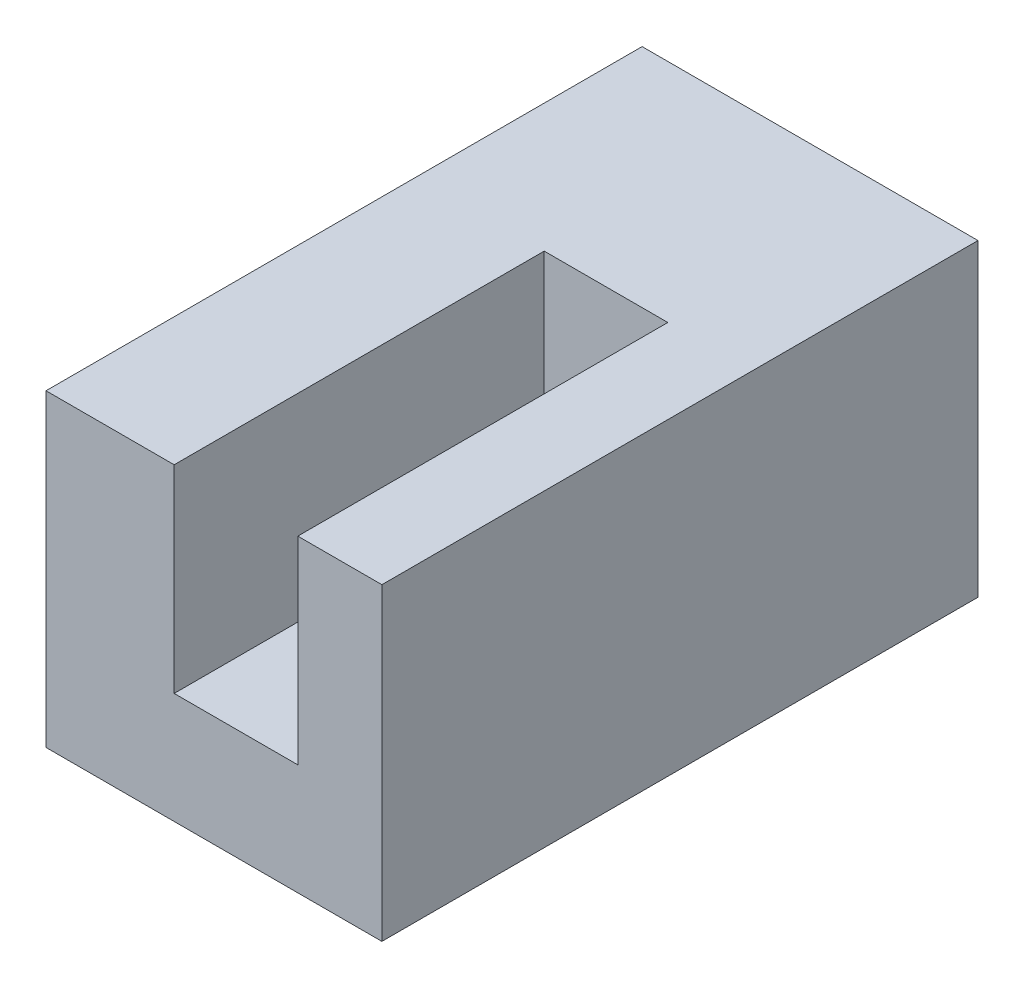
SolidWorks part; units mm, degrees
ref_plane "Piano frontale" through (0, 0, 0) normal (0, 0, 1) x (1, 0, 0)
ref_plane "Piano superiore" through (0, 0, 0) normal (0, 1, 0) x (1, 0, 0)
ref_plane "Piano destro" through (0, 0, 0) normal (1, 0, 0) x (0, 0, -1)
sketch "Schizzo1" plane through (0, 0, 0) normal (0, 0, 1) x (1, 0, 0)
  line L1 (0, 0) -> (3994, 0)
  line L2 (0, 0) -> (0, 3673.5)
  line L3 (0, 3673.5) -> (3994, 3673.5)
  line L4 (3994, 0) -> (3994, 3673.5)
  dimension "D1" = 3994
  dimension "D2" = 3673.5
extrude "Estrusione-Estrusione1" add sketch "Schizzo1" against normal blind 7088
sketch "Schizzo2" plane through (0, 0, 0) normal (0, 0, 1) x (1, 0, 0)
  line L0 (3994, 2436.8171) -> (2994, 2436.8171) construction
  line L1 (3994, 0) -> (3994, 3673.5) construction
  line L2 (2994, 0) -> (2994, 1318.5) construction
  line L3 (0, 0) -> (3994, 0) construction
  line L4 (3994, 3673.5) -> (0, 3673.5) construction
  line L5 (2994, 1318.5) -> (1524, 1318.5)
  line L6 (2994, 1318.5) -> (2994, 3673.5)
  line L7 (2994, 3673.5) -> (1524, 3673.5)
  line L8 (1524, 1318.5) -> (1524, 3673.5)
  dimension "D1" = 1000
  dimension "D2" = 1318.5
  dimension "D3" = 1470
extrude "Taglio-Estrusione1" cut sketch "Schizzo2" against normal blind 4400
